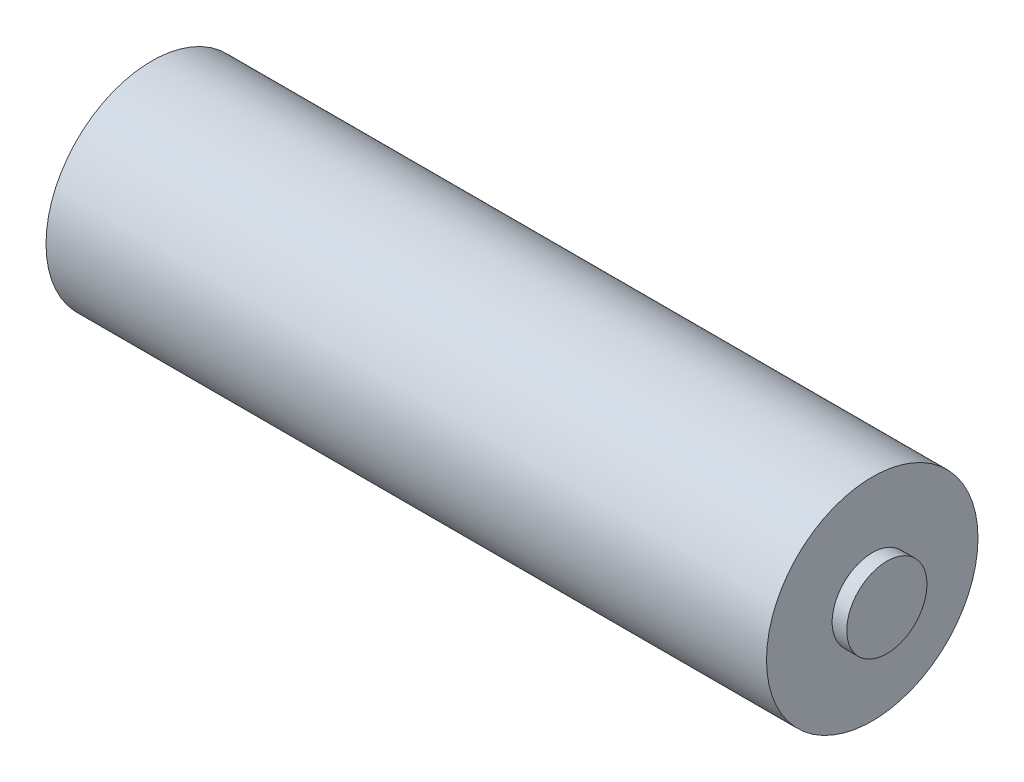
SolidWorks part; units mm, degrees
material "ABS"
ref_plane "Front" through (0, 0, 0) normal (0, 0, 1) x (1, 0, 0)
ref_plane "Top" through (0, 0, 0) normal (0, 1, 0) x (1, 0, 0)
ref_plane "Right" through (0, 0, 0) normal (1, 0, 0) x (0, 0, -1)
sketch "Sketch1" plane through (0, 0, 0) normal (1, 0, 0) x (0, 0, -1)
  circle A0 centre (0, 0) radius 7.25
  dimension "D1" = 14.5
extrude "Boss-Extrude1" add sketch "Sketch1" along normal blind 49.4
sketch "Sketch2" plane through (49.4, 0, 0) normal (1, 0, 0) x (0, 0, -1)
  circle A0 centre (0, 0) radius 2.75
  dimension "D1" = 5.5
extrude "Boss-Extrude2" add sketch "Sketch2" along normal blind 1
sketch "Sketch3" plane through (0, 0, 0) normal (-1, 0, 0) x (0, 0, 1)
  circle A0 centre (0, 0) radius 3.5
  dimension "D1" = 7
extrude "Boss-Extrude3" add sketch "Sketch3" along normal blind 0.1
fillet "Fillet1" radius 0.2 1 edges at (0, 0, -3.5)
